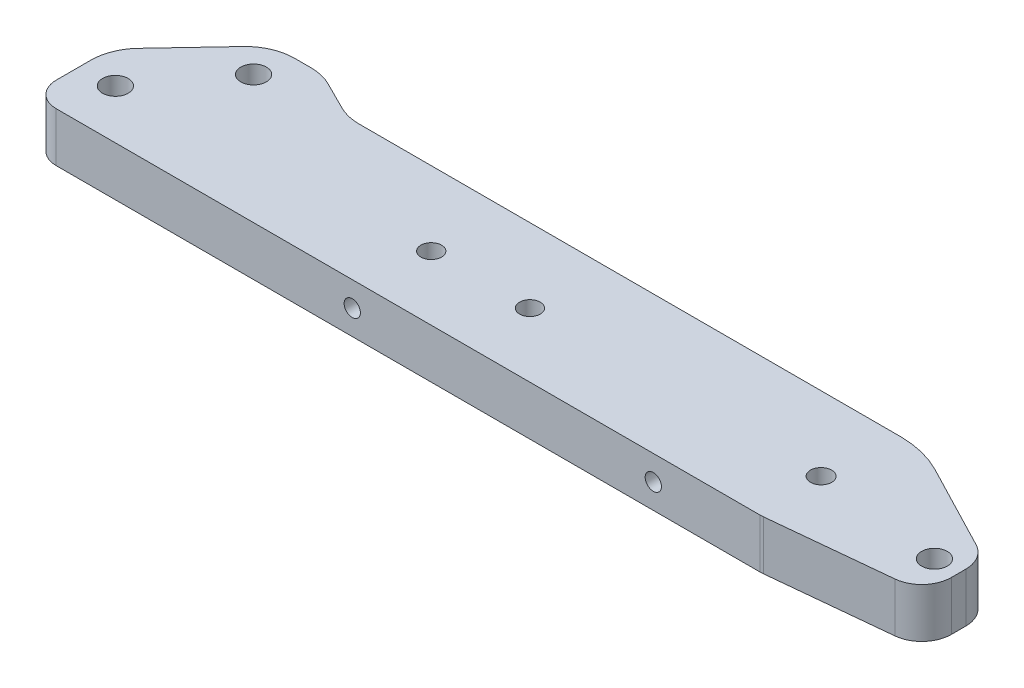
SolidWorks part; units mm, degrees
material "PE High Density"
ref_plane "Front Plane" through (0, 0, 0) normal (0, 0, 1) x (1, 0, 0)
ref_plane "Top Plane" through (0, 0, 0) normal (0, 1, 0) x (1, 0, 0)
ref_plane "Right Plane" through (0, 0, 0) normal (1, 0, 0) x (0, 0, -1)
sketch "Sketch1" plane through (0, 0, 0) normal (0, 1, 0) x (1, 0, 0)
  line L0 (159.9654, 15) -> (134.9654, 28)
  line L5 (159.9654, 3) -> (129.9654, 0)
  line L7 (-18, 16) -> (-18, 0)
  line L8 (-18, 0) -> (0, 0)
  line L9 (0, 0) -> (129.9654, 0)
  line L10 (159.9654, 3) -> (159.9654, 15)
  line L12 (-18, 16) -> (-2, 33)
  line L13 (-2, 33) -> (8, 33)
  line L14 (8, 33) -> (18, 28)
  line L15 (18, 28) -> (134.9654, 28)
  circle A0 centre (-11, 10) radius 2.6
  circle A1 centre (129, 13) radius 2.15
  circle A3 centre (154.9654, 10) radius 2.6
  circle A4 centre (1, 26) radius 2.6
  circle A6 centre (50, 13) radius 2.1
  circle A7 centre (70, 13) radius 2.1
  dimension "D9" = 5.2
  dimension "D12" = 4.3
  dimension "D13" = 5.2
  dimension "D20" = 10
  dimension "D14" = 5.2
  dimension "D30" = 4.2
  dimension "D31" = 4.2
  dimension "D4" = 3
  dimension "D5" = 30
  dimension "D6" = 25
  dimension "D7" = 18
  dimension "D8" = 16
  dimension "D10" = 7
  dimension "D11" = 10
  dimension "D16" = 5
  dimension "D19" = 33
  dimension "D21" = 10
  dimension "D25" = 20
  dimension "D26" = 28
  dimension "D33" = 16
  dimension "D34" = 13
  dimension "D35" = 10
  dimension "D36" = 12
  dimension "D37" = 0
extrude "Boss-Extrude1" add sketch "Sketch1" along normal blind 10
fillet "Fillet1" radius 5 1 edges at (-18, 5, 0)
fillet "Fillet2" radius 6 3 edges at (129.9654, 5, 0) (159.9654, 5, -3) (159.9654, 5, -15)
fillet "Fillet3" radius 10 2 edges at (-2, 5, -33) (-18, 5, -16)
fillet "Fillet4" radius 20 1 edges at (134.9654, 5, -28)
fillet "Fillet5" radius 10 2 edges at (18, 5, -28) (8, 5, -33)
sketch "Sketch2" plane through (0, 0, 0) normal (0, 0, 1) x (1, 0, 0)
  line L0 (-13, 10) -> (-13, 0) construction
  line L1 (-13, 0) -> (129.6661, 0) construction
  circle A0 centre (47, 5) radius 1.65
  circle A1 centre (108, 5) radius 1.65
  dimension "D3" = 3.3
  dimension "D5" = 3.3
  dimension "D1" = 60
  dimension "D2" = 5
  dimension "D4" = 61
extrude "Cut-Extrude1" cut sketch "Sketch2" against normal blind 10
